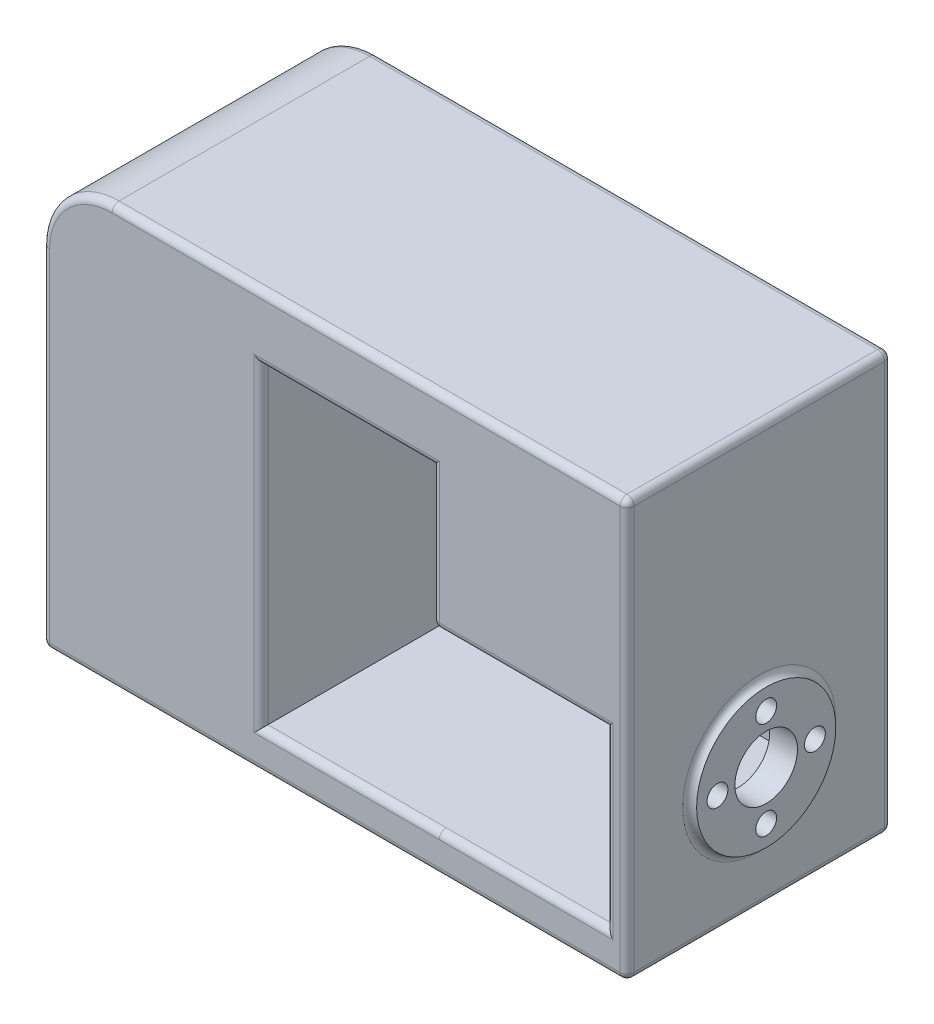
SolidWorks part; units mm, degrees
ref_plane "Front Plane" through (0, 0, 0) normal (0, 0, 1) x (1, 0, 0)
ref_plane "Top Plane" through (0, 0, 0) normal (0, 1, 0) x (1, 0, 0)
ref_plane "Right Plane" through (0, 0, 0) normal (1, 0, 0) x (0, 0, -1)
sketch "Sketch1" plane through (0, 0, 0) normal (0, 0, 1) x (1, 0, 0)
  line L1 (-72.4692, 42.4237) -> (1.5308, 42.4237)
  line L2 (-82.4692, 32.4237) -> (-82.4692, -17.5763)
  line L3 (-82.4692, -17.5763) -> (1.5308, -17.5763)
  line L4 (1.5308, 42.4237) -> (1.5308, -17.5763)
  arc A1 (-72.4692, 42.4237) -> (-82.4692, 32.4237) centre (-72.4692, 32.4237) ccw
  point P8 (-82.4692, 42.4237)
  dimension "D5" = 10
  dimension "D1" = 84
  dimension "D2" = 60
extrude "Boss-Extrude1" add sketch "Sketch1" along normal blind 38
sketch "Sketch2" plane through (0, 0, 38) normal (0, 0, 1) x (1, 0, 0)
  line L0 (-51.0806, 0.4237) -> (-26.4506, 0.4237) construction
  line L1 (-51.0806, 33.0537) -> (-26.4506, 33.0537)
  line L2 (-51.0806, 33.0537) -> (-51.0806, -12.0763)
  line L3 (-51.0806, -12.0763) -> (-26.4506, -12.0763)
  line L4 (-26.4506, 33.0537) -> (-26.4506, -12.0763)
  line L5 (1.5308, 42.4237) -> (-72.4692, 42.4237) construction
  dimension "D1" = 24.63
  dimension "D2" = 45.13
  dimension "D3" = 12.5
  dimension "D4" = 42
extrude "Cut-Extrude1" cut sketch "Sketch2" against normal blind 35
sketch "Sketch3" plane through (0, 0, 3) normal (0, 0, 1) x (1, 0, 0)
  line L0 (-51.0806, 33.0537) -> (-51.0806, -12.0763) construction
  line L1 (-51.0806, 18.0537) -> (-26.4506, 18.0537)
  line L2 (-51.0806, 18.0537) -> (-51.0806, 2.9237)
  line L3 (-51.0806, 2.9237) -> (-26.4506, 2.9237)
  line L4 (-26.4506, 18.0537) -> (-26.4506, 2.9237)
  line L5 (-26.4506, -12.0763) -> (-26.4506, 33.0537) construction
  line L6 (-26.4506, 33.0537) -> (-51.0806, 33.0537) construction
  line L7 (-51.0806, -12.0763) -> (-26.4506, -12.0763) construction
  dimension "D1" = 15
  dimension "D2" = 15
extrude "Cut-Extrude2" cut sketch "Sketch3" against normal blind 35
fillet "Fillet1" radius 1 21 edges at (-26.4506, 10.4887, 0) (-38.7656, 2.9237, 0) (-51.0806, 10.4887, 0) (-38.7656, 18.0537, 0) (-40.4692, -17.5763, 0) (1.5308, -17.5763, 19) (1.5308, 12.4237, 0) (1.5308, 42.4237, 19) (-35.4692, 42.4237, 0) (-79.5403, 39.4948, 0) (-82.4692, -17.5763, 19) (-82.4692, 7.4237, 0) (-40.4692, -17.5763, 38) (-82.4692, 7.4237, 38) (-79.5403, 39.4948, 38) (-35.4692, 42.4237, 38) (1.5308, 12.4237, 38) (-38.7656, -12.0763, 38) (-26.4506, 10.4887, 38) (-38.7656, 33.0537, 38) (-51.0806, 10.4887, 38)
sketch "Sketch4" plane through (1.5308, 0, 0) normal (1, 0, 0) x (0, 0, -1)
  line L0 (-37, 42.4237) -> (-1, 42.4237) construction
  line L1 (-19, 41.4237) -> (-19, -16.5763) construction
  line L2 (-1, 41.4237) -> (-37, 41.4237) construction
  line L3 (-37, -16.5763) -> (-1, -16.5763) construction
  circle A0 centre (-19, 0.4237) radius 10
  point P10 (-19, 0.4237)
  dimension "D1" = 20
  dimension "D2" = 42
extrude "Boss-Extrude2" add sketch "Sketch4" along normal blind 1
fillet "Fillet3" radius 1 1 edges at (1.5308, -9.5763, 19)
sketch "Sketch5" plane through (2.5308, 0, 0) normal (1, 0, 0) x (0, 0, -1)
  line L0 (-29, 0.4237) -> (-9, 0.4237) construction
  line L1 (-19, -9.5763) -> (-19, 10.4237) construction
  circle A0 centre (-19, 7.4237) radius 1.5
  circle A1 centre (-19, 0.4237) radius 10 construction
  circle A2 centre (-12, 0.4237) radius 1.5
  circle A3 centre (-19, -6.5763) radius 1.5
  circle A4 centre (-26, 0.4237) radius 1.5
  circle A5 centre (-19, 0.4237) radius 4.5
  point P17 (-19, 0.4237)
  dimension "D1" = 3
  dimension "D3" = 4
  dimension "D4" = 9
  dimension "D2" = 7
extrude "Cut-Extrude3" cut sketch "Sketch5" against normal blind 21
sketch "Sketch6" plane through (0, 0, 38) normal (0, 0, 1) x (1, 0, 0)
  line L1 (-26.4506, -12.0763) -> (-1.4692, -12.0763)
  line L2 (-26.4506, -12.0763) -> (-26.4506, 12.9237)
  line L3 (-26.4506, 12.9237) -> (-1.4692, 12.9237)
  line L4 (-1.4692, -12.0763) -> (-1.4692, 12.9237)
  line L5 (-26.4506, -12.0763) -> (-26.4506, 33.0537) construction
  line L8 (-51.0806, -12.0763) -> (-26.4506, -12.0763) construction
  line L9 (1.5308, 41.4237) -> (1.5308, -16.5763) construction
  point P8 (0, 0)
  dimension "D1" = 3
  dimension "D2" = 25
extrude "Cut-Extrude4" cut sketch "Sketch6" against normal blind 35
fillet "Fillet2" radius 1 2 edges at (-38.7656, 2.9237, 3) (-38.7656, 18.0537, 3)
fillet "Fillet4" radius 1 6 edges at (-26.4506, 12.9237, 20) (-26.1577, 12.9237, 37.7071) (-26.4506, 7.4237, 3) (-13.4599, 12.9237, 38) (-13.4599, -12.0763, 38) (-1.4692, 0.4237, 38)
